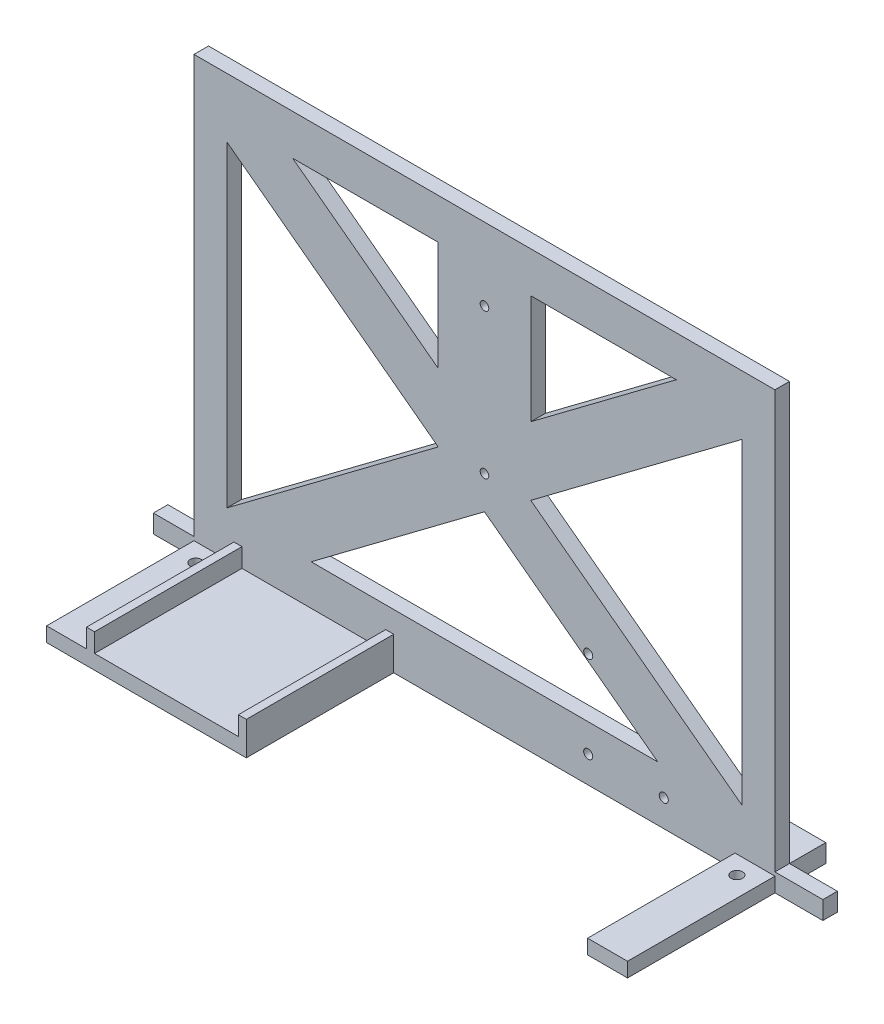
SolidWorks part; units mm, degrees
ref_plane "Front" through (0, 0, 0) normal (0, 0, 1) x (1, 0, 0)
ref_plane "Top" through (0, 0, 0) normal (0, 1, 0) x (1, 0, 0)
ref_plane "Right" through (0, 0, 0) normal (1, 0, 0) x (0, 0, -1)
sketch "Sketch1" plane through (0, 0, 0) normal (0, 0, 1) x (1, 0, 0)
  line L0 (-90.1289, 55.4552) -> (-90.1289, -55.4552)
  line L1 (-101.6, 76.2) -> (101.6, 76.2)
  line L2 (-101.6, 76.2) -> (-101.6, -76.2)
  line L3 (-101.6, -76.2) -> (101.6, -76.2)
  line L4 (101.6, 76.2) -> (101.6, -76.2)
  line L5 (-101.6, 76.2) -> (101.6, -76.2) construction
  line L6 (-101.6, -76.2) -> (101.6, 76.2) construction
  line L7 (0, -55) -> (0, 55) construction
  line L8 (-90.1289, -55.4552) -> (-16.1887, 0)
  line L9 (-16.1887, 0) -> (-90.1289, 55.4552)
  line L10 (55, 0) -> (-55, 0) construction
  line L11 (16.1887, 0) -> (90.1289, 55.4552)
  line L12 (90.1289, -55.4552) -> (16.1887, 0)
  line L13 (90.1289, 55.4552) -> (90.1289, -55.4552)
  line L14 (-16.1887, 61.9912) -> (-16.1887, 23.8125)
  line L15 (-16.1887, 23.8125) -> (-67.0937, 61.9912)
  line L16 (-67.0937, 61.9912) -> (-16.1887, 61.9912)
  line L17 (16.1887, 23.8125) -> (67.0937, 61.9912)
  line L18 (16.1887, 61.9912) -> (16.1887, 23.8125)
  line L19 (67.0937, 61.9912) -> (16.1887, 61.9912)
  line L20 (-60.6282, -57.0175) -> (0, -11.5463)
  line L21 (0, -11.5463) -> (60.6282, -57.0175)
  line L22 (60.6282, -57.0175) -> (-60.6282, -57.0175)
  circle A0 centre (0, 50.8) radius 1.5
  circle A2 centre (0, 0) radius 1.5
  point P0 (0, 0)
  dimension "D3" = 3
  dimension "D4" = 50.8
  dimension "D6" = 19.05
  dimension "D1" = 203.2
  dimension "D2" = 152.4
  dimension "D5" = 25.4
extrude "Boss-Extrude1" add sketch "Sketch1" along normal blind 5.08 contours L4 L1 L2 L3 A2 A0 L19 L17 L18 L9 L8 L0 L11 L13 L12 L15 L16 L14 L21 L22 L20 region at (0, 73.66, 0)
sketch "Sketch2" plane through (0, 0, 5.08) normal (0, 0, 1) x (1, 0, 0)
  line L0 (-101.6, -76.2) -> (101.6, -76.2) construction
  line L1 (-101.6, -76.2) -> (-87.63, -76.2)
  line L2 (-101.6, -76.2) -> (-101.6, -71.12)
  line L3 (-101.6, -71.12) -> (-87.63, -71.12)
  line L4 (-87.63, -76.2) -> (-87.63, -71.12)
  line L5 (0, -55) -> (0, 55) construction
  line L6 (101.6, -71.12) -> (87.63, -71.12)
  line L7 (87.63, -76.2) -> (87.63, -71.12)
  line L8 (101.6, -76.2) -> (87.63, -76.2)
  line L9 (101.6, -76.2) -> (101.6, -71.12)
  line L11 (-87.63, -71.12) -> (-31.75, -71.12)
  line L12 (-87.63, -71.12) -> (-87.63, -76.2)
  line L13 (-87.63, -76.2) -> (-31.75, -76.2)
  line L14 (-31.75, -71.12) -> (-31.75, -76.2)
  line L15 (-87.63, -71.12) -> (-84.836, -71.12)
  line L16 (-87.63, -71.12) -> (-87.63, -64.5258)
  line L17 (-87.63, -64.5258) -> (-84.836, -64.5258)
  line L18 (-84.836, -71.12) -> (-84.836, -64.5258)
  line L19 (-31.75, -71.12) -> (-34.544, -71.12)
  line L20 (-31.75, -71.12) -> (-31.75, -64.5258)
  line L21 (-31.75, -64.5258) -> (-34.544, -64.5258)
  line L22 (-34.544, -71.12) -> (-34.544, -64.5258)
  line M10 (-101.6, -76.2) -> (101.6, -76.2)
  dimension "D1" = 5.08
  dimension "D2" = 55.88
  dimension "D3" = 50.292
  dimension "D4" = 13.97
  dimension "D5" = 31.75
extrude "Boss-Extrude2" add sketch "Sketch2" along normal blind 51.562 contours L4 L3 L2 M10 | L14 L11 L4 M10 | L9 L6 L7 M10 | L16 L15 L18 L17 | L20 L19 L22 L21 region at (-94.615, -73.66, 5.08) region at (94.615, -73.66, 5.08) region at (-59.69, -73.66, 5.08)
sketch "Sketch3" plane through (0, -71.12, 0) normal (0, 1, 0) x (1, 0, 0)
  line L4 (0, -2.794) -> (0, 2.794) construction
  line L10 (-101.6, -5.08) -> (-87.63, -5.08) construction
  line L11 (-101.6, -56.642) -> (-101.6, -5.08) construction
  circle A0 centre (-94.615, -11.43) radius 2
  circle A1 centre (94.615, -11.43) radius 2
  dimension "D1" = 4
  dimension "D2" = 6.35
  dimension "D3" = 6.985
extrude "Cut-Extrude1" cut sketch "Sketch3" against normal up to vertex (5.08 mm away) contours A0 | A1 region at (-94.615, -71.12, 11.43) region at (94.615, -71.12, 11.43) up to point (-101.6, -76.2, 56.642)
sketch "Sketch4" plane through (0, 0, 0) normal (0, 0, -1) x (-1, 0, 0)
  line L0 (0, 31.1531) -> (0, -31.1531) construction
  line L1 (-101.6, -76.2) -> (-88.9, -76.2)
  line L2 (-101.6, -76.2) -> (-101.6, -69.85)
  line L3 (-101.6, -69.85) -> (-88.9, -69.85)
  line L4 (-101.6, 76.2) -> (-101.6, -76.2)
  line L5 (-101.6, -76.2) -> (101.6, -76.2)
  line L6 (101.6, -76.2) -> (101.6, 76.2)
  line L7 (101.6, 76.2) -> (-101.6, 76.2)
  line L8 (-101.6, 76.2) -> (-101.6, -76.2)
  line L9 (-101.6, -76.2) -> (101.6, -76.2)
  line L10 (101.6, -76.2) -> (101.6, 76.2)
  line L11 (101.6, 76.2) -> (-101.6, 76.2)
  line L12 (-88.9, -76.2) -> (-88.9, -69.85)
  line L13 (101.6, -69.85) -> (88.9, -69.85)
  line L14 (88.9, -76.2) -> (88.9, -69.85)
  line L15 (101.6, -76.2) -> (88.9, -76.2)
  line L16 (101.6, -76.2) -> (101.6, -69.85)
  dimension "D2" = 12.7
  dimension "D3" = 6.35
  dimension "D1" = 0
extrude "Boss-Extrude3" add sketch "Sketch4" along normal blind 12.7 contours L2 L1 L12 L3 | L16 L13 L14 L15
sketch "Sketch5" plane through (101.6, 0, 0) normal (1, 0, 0) x (0, 0, -1)
  line L1 (0, -69.85) -> (-5.08, -69.85)
  line L2 (0, -69.85) -> (0, -76.2)
  line L3 (0, -76.2) -> (-5.08, -76.2)
  line L4 (-5.08, -69.85) -> (-5.08, -76.2)
extrude "Boss-Extrude4" add sketch "Sketch5" along normal blind 16.764
sketch "Sketch6" plane through (-101.6, 0, 0) normal (-1, 0, 0) x (0, 0, 1)
  line L1 (0, -69.85) -> (5.08, -69.85)
  line L2 (0, -69.85) -> (0, -76.2)
  line L3 (0, -76.2) -> (5.08, -76.2)
  line L4 (5.08, -69.85) -> (5.08, -76.2)
extrude "Boss-Extrude5" add sketch "Sketch6" along normal blind 14.224
sketch "Sketch7" plane through (0, 0, 5.08) normal (0, 0, 1) x (1, 0, 0)
  circle A0 centre (36.2876, -66.7853) radius 1.5875
  circle A1 centre (36.2876, -36.4323) radius 1.5875
  circle A3 centre (62.7036, -66.7853) radius 1.5875
  dimension "D1" = 3.175
  dimension "D2" = 30.353
  dimension "D3" = 26.416
extrude "Cut-Extrude2" cut sketch "Sketch7" against normal up to next
